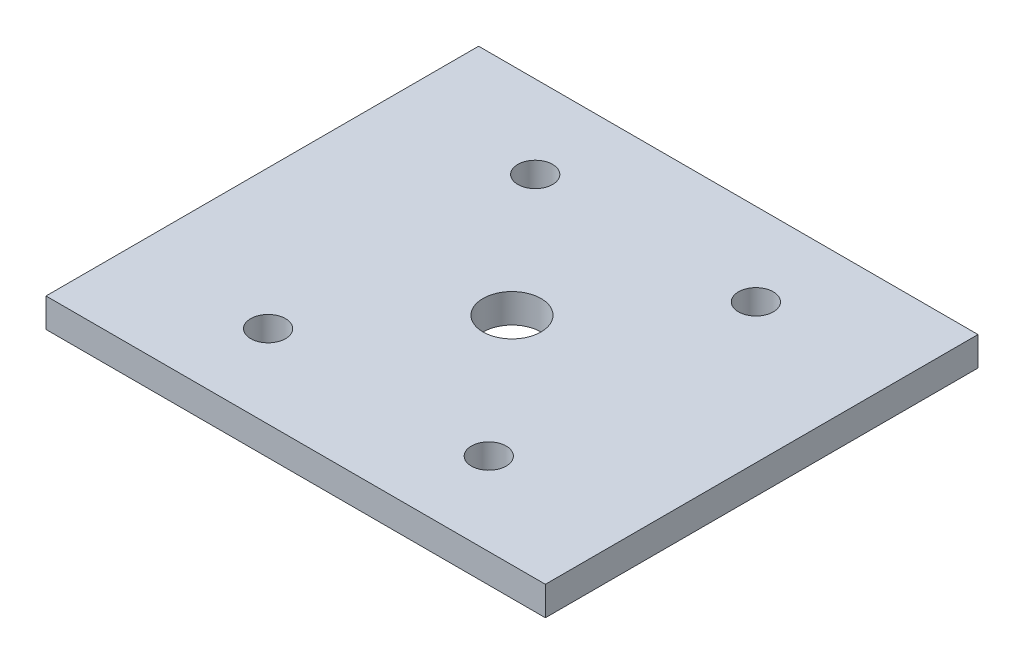
SolidWorks part; units mm, degrees
note: The reader was unsure of these and kept them because the rebuilt part matched: thickness of "Base-Flange2", "Sheet-Metal6", "Sheet-Metal10".
material "Stainless Steel (ferritic)"
ref_plane "Front Plane" through (0, 0, 0) normal (0, 0, 1) x (1, 0, 0)
ref_plane "Top Plane" through (0, 0, 0) normal (0, 1, 0) x (1, 0, 0)
ref_plane "Right Plane" through (0, 0, 0) normal (1, 0, 0) x (0, 0, -1)
sketch "Sketch7" plane through (0, 0, 0) normal (0, 1, 0) x (1, 0, 0)
  line L0 (133, -142.5901) -> (133, 199.2611) construction
  line L1 (-39, 0) -> (133, 0)
  line L2 (-39, 0) -> (-39, 149)
  line L3 (-39, 149) -> (133, 149)
  line L4 (133, 0) -> (133, 149)
  line L5 (-39, 149) -> (-39, -97) construction
  line L6 (-17.2, 149) -> (-35.8, 149) construction
  dimension "D2" = 149
base flange "Base-Flange2" sketch "Sketch7" thickness 10 reverse thickness direction no parameters "D1"=0.7366
ref_plane "Plane1" through (47, 0, 0) normal (-1, 0, 0) x (0, 0, 1)
ref_plane "Plane2" through (0, 0, -74.5) normal (0, 0, 1) x (1, 0, 0)
sketch "Sketch8" plane through (0, 0, 0) normal (0, 1, 0) x (1, 0, 0)
  line L0 (-39, 0) -> (133, 149) construction
  line L5 (85, 120.5) -> (85, 28.5) construction
  line L6 (85, 120.5) -> (9, 120.5) construction
  line L7 (9, 120.5) -> (9, 28.5) construction
  line L8 (85, 28.5) -> (9, 28.5) construction
  line L9 (85, 120.5) -> (9, 28.5) construction
  line L10 (9, 120.5) -> (85, 28.5) construction
  circle A0 centre (9, 28.5) radius 6
  circle A1 centre (9, 120.5) radius 6
  circle A2 centre (85, 120.5) radius 6
  circle A3 centre (85, 28.5) radius 6
  circle A8 centre (47, 74.5) radius 10
  point P2 (47, 74.5)
  point P3 (47, 74.5)
  dimension "D2" = 20
  dimension "D4" = 12
  dimension "D1" = 76
  dimension "D3" = 92
extrude "Cut-Extrude1" cut sketch "Sketch8" against normal through all contours A1 | A2 | A0 | A8 | A3 normal cut yes
sketch "Bend-Lines5" [suppressed] plane through (0, 0, 0) normal (0, 1, 0) x (1, 0, 0)
sketch "Bounding-Box5" [suppressed] plane through (0, 0, 0) normal (0, 1, 0) x (1, 0, 0)
sheet metal parameters "Sheet-Metal6" thickness 10 parameters "D1"=0.7366
flat pattern "Flat-Pattern6" [suppressed]
sketch "Bend-Lines6" plane through (0, 0, 0) normal (0, 1, 0) x (1, 0, 0)
sketch3d "Bounding-Box6" [suppressed]
  line L0 (0, 0, 0) -> (0, 149, 0) construction
  line L1 (133, 0, 0) -> (133, 149, 0) construction
  line L2 (0, 0, 0) -> (133, 0, 0) construction
  line L3 (0, 149, 0) -> (133, 149, 0) construction
sheet metal parameters "Sheet-Metal10" thickness 10 parameters "D1"=0.7366
flat pattern "Flat-Pattern6"
sketch "Bend-Lines6" plane through (0, 0, 0) normal (0, 1, 0) x (1, 0, 0)
sketch3d "Bounding-Box6" [suppressed]
  line L0 (133, 149, 0) -> (-39, 149, 0) construction
  line L1 (133, 0, 0) -> (-39, 0, 0) construction
  line L2 (133, 149, 0) -> (133, 0, 0) construction
  line L3 (-39, 149, 0) -> (-39, 0, 0) construction
